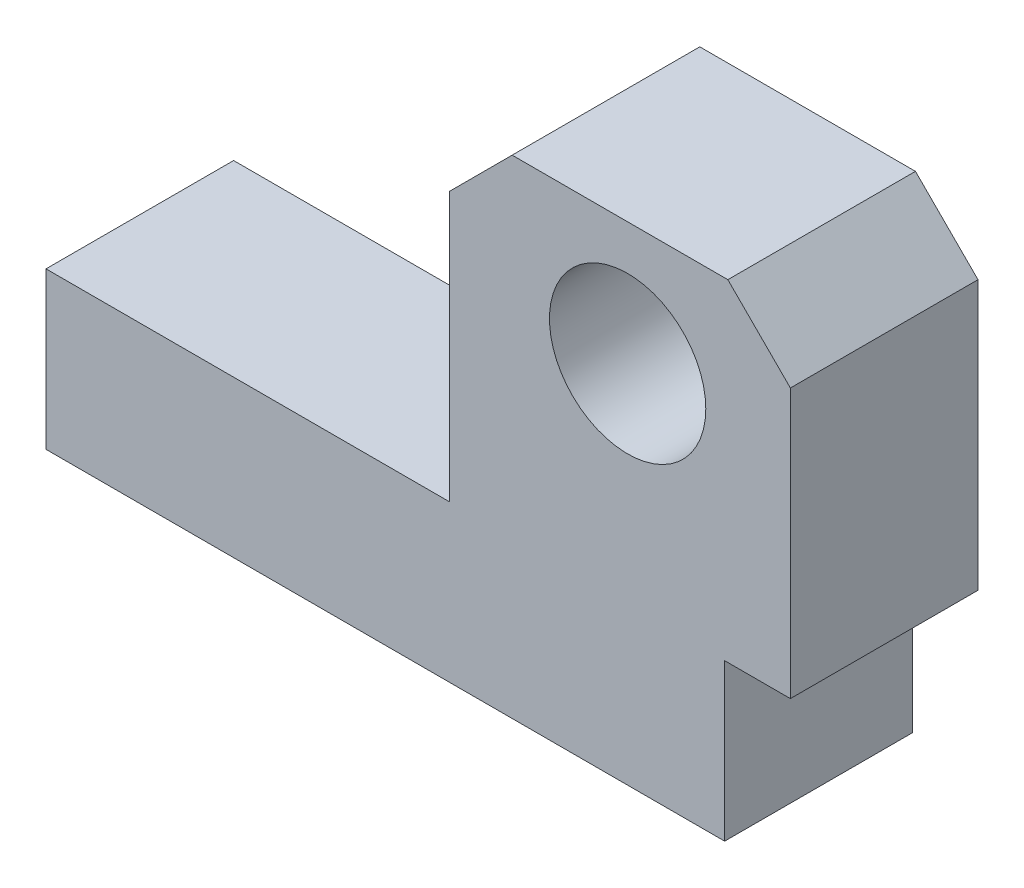
SolidWorks part; units mm, degrees
ref_plane "Спереди" through (0, 0, 0) normal (0, 0, 1) x (1, 0, 0)
ref_plane "Сверху" through (0, 0, 0) normal (0, 1, 0) x (1, 0, 0)
ref_plane "Справа" through (0, 0, 0) normal (1, 0, 0) x (0, 0, -1)
sketch "Эскиз1" plane through (0, 0, 0) normal (0, 0, 1) x (1, 0, 0)
  line L0 (-4.7304, 5) -> (8.1773, 5)
  line L1 (-4.7304, 0) -> (16.9727, 0)
  line L2 (-4.7304, 0) -> (-4.7304, 5)
  line L3 (10.1773, 15.603) -> (17.0753, 15.603)
  line L4 (19.0753, 5) -> (19.0753, 13.603)
  line L5 (8.1773, 5) -> (8.1773, 13.603)
  line L6 (-30.1123, 0) -> (34.8877, 0) construction
  line L7 (8.1773, 13.603) -> (10.1773, 15.603)
  line L8 (17.0753, 15.603) -> (19.0753, 13.603)
  line L9 (16.9727, 0) -> (16.9727, 5)
  line L10 (16.9727, 5) -> (19.0753, 5)
  circle A0 centre (13.8703, 11.6742) radius 2.5
  point P1 (8.1773, 15.603)
  point P7 (19.0753, 15.603)
  dimension "D1" = 5
  dimension "D4" = 2
  dimension "D5" = 2
extrude "Вытянуть1" add sketch "Эскиз1" along normal blind 6
